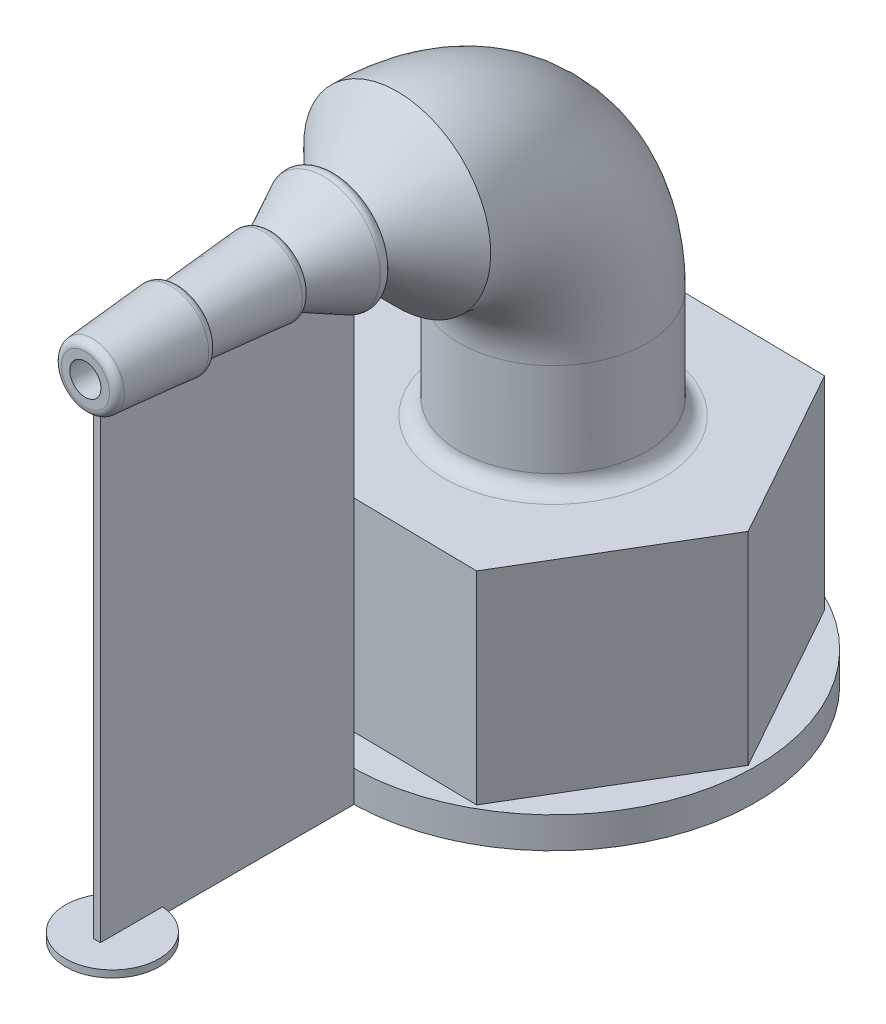
SolidWorks part; units mm, degrees
ref_plane "Спереди" through (0, 0, 0) normal (0, 0, 1) x (1, 0, 0)
ref_plane "Сверху" through (0, 0, 0) normal (0, 1, 0) x (1, 0, 0)
ref_plane "Справа" through (0, 0, 0) normal (1, 0, 0) x (0, 0, -1)
sketch "Эскиз1" plane through (0, 0, 0) normal (0, 1, 0) x (1, 0, 0)
  line L1 (6.511, 10.906) -> (-6.1893, 11.0917)
  line L2 (-6.1893, 11.0917) -> (-12.7003, 0.1857)
  line L3 (-12.7003, 0.1857) -> (-6.511, -10.906)
  line L4 (-6.511, -10.906) -> (6.1893, -11.0917)
  line L5 (6.1893, -11.0917) -> (12.7003, -0.1857)
  line L6 (12.7003, -0.1857) -> (6.511, 10.906)
  circle A0 centre (0, 0) radius 4.75
  circle A1 centre (0, 0) radius 11 construction
  dimension "D1" = 9.5
  dimension "D2" = 22
extrude "Бобышка-Вытянуть1" add sketch "Эскиз1" along normal blind 13
sketch "Эскиз2" plane through (0, 0, 0) normal (0, -1, 0) x (1, 0, 0)
  circle A0 centre (0, 0) radius 4.77
  circle A1 centre (0, 0) radius 13
  dimension "D1" = 26
extrude "Бобышка-Вытянуть2" add sketch "Эскиз2" along normal blind 2
sketch "Эскиз3" plane through (0, 0, 0) normal (1, 0, 0) x (0, 0, -1)
  line L0 (0, 0) -> (0, 20) construction
  line L1 (-10, 30) -> (-30, 30) construction
  line L2 (-30, 30) -> (-10, 30)
  line L3 (0, 20) -> (0, 13)
  line L4 (-0.1857, 13) -> (10.906, 13) construction
  arc A0 (-10, 30) -> (0, 20) centre (-10, 20) cw construction
  arc A1 (-10, 30) -> (0, 20) centre (-10, 20) cw
  point P6 (0, 30)
  dimension "D3" = 10
  dimension "D1" = 30
  dimension "D2" = 30
sketch "Эскиз4" plane through (0, 13, 0) normal (0, 1, 0) x (1, 0, 0)
  circle A0 centre (0, 0) radius 6
  circle A1 centre (0, 0) radius 1
  dimension "D1" = 12
  dimension "D2" = 2
sweep "По траектории1" add profiles "Эскиз4" path "Эскиз3"
fillet "Скругление1" radius 1 1 edges at (0, 13, 6)
chamfer "Фаска1" distance 4 angle 45 1 edges at (0, 13, 1)
sketch "Эскиз5" plane through (0, 0, 0) normal (1, 0, 0) x (0, 0, -1)
  line L0 (-30, 30) -> (-8.4128, 30) construction
  line L1 (-30, 36) -> (-30, 24) construction
  line L2 (-30, 32) -> (-24, 32.5)
  line L4 (-24, 32.5) -> (-24, 32)
  line L5 (-24, 32) -> (-18, 32.5)
  line L6 (-18, 32.5) -> (-18, 32)
  line L8 (-30, 32) -> (-30, 36)
  line L9 (-30, 36) -> (-10, 36)
  line L10 (-18, 32) -> (-14, 34)
  line L11 (-14, 34) -> (-14, 32)
  line L12 (-14, 32) -> (-10, 36)
  point P6 (0, 0)
  dimension "D1" = 4
  dimension "D2" = 5
  dimension "D3" = 12
  dimension "D4" = 8
  dimension "D5" = 16
revolve "Вырез-Повернуть1" cut sketch "Эскиз5" angle 360 about L0
fillet "Скругление2" radius 0.5 4 edges at (4, 30, 14) (2.5, 30, 18) (2.5, 30, 24) (2, 30, 30)
sketch "Эскиз6" plane through (0, 0, 0) normal (1, 0, 0) x (0, 0, -1)
  line L0 (-29.2603, -2) -> (-29.2603, 27.9384)
  line L1 (-29.5415, 27.9618) -> (-24.5396, 27.545) construction
  line L2 (-29.2603, 27.9384) -> (-13, 27.9384)
  line L3 (-13, 27.9384) -> (-13, -2)
  line L4 (-13, -2) -> (-29.2603, -2)
extrude "Бобышка-Вытянуть4" add sketch "Эскиз6" along normal mid plane 0.45 separate body
sketch "Эскиз7" plane through (0, -2, 0) normal (0, -1, 0) x (1, 0, 0)
  circle A0 centre (0, 28.2706) radius 3
  dimension "D1" = 6
extrude "Бобышка-Вытянуть5" add sketch "Эскиз7" against normal blind 0.45
